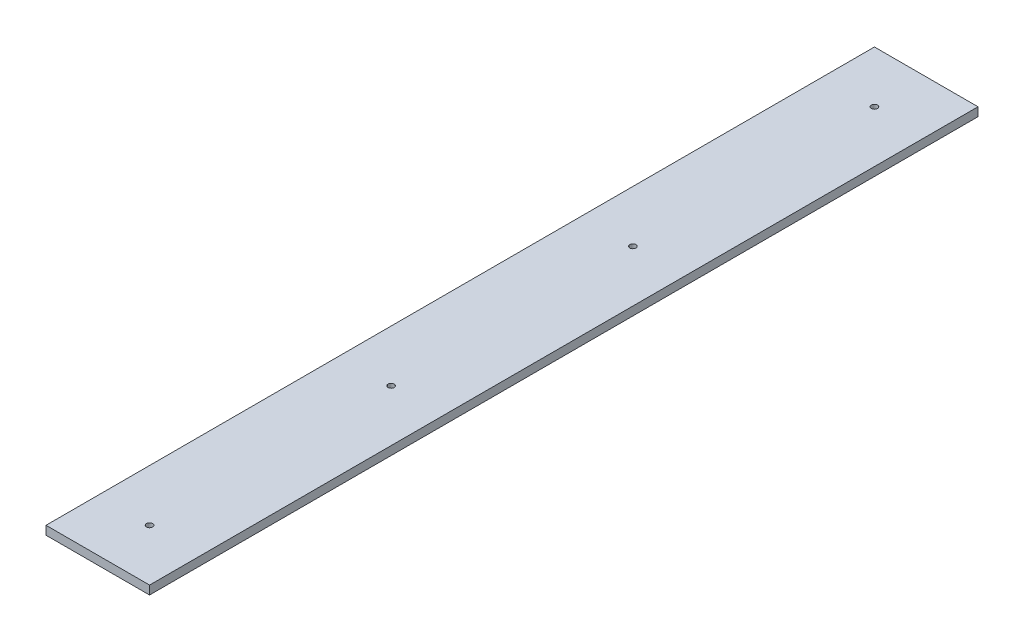
SolidWorks part; units mm, degrees
material "6061 Alloy"
ref_plane "Front Plane" through (0, 0, 0) normal (0, 0, 1) x (1, 0, 0)
ref_plane "Top Plane" through (0, 0, 0) normal (0, 1, 0) x (1, 0, 0)
ref_plane "Right Plane" through (0, 0, 0) normal (1, 0, 0) x (0, 0, -1)
sketch "Sketch1" plane through (0, 0, 0) normal (0, 1, 0) x (1, 0, 0)
  line L1 (0, 0) -> (76.2, 0)
  line L2 (0, 0) -> (0, 609.6)
  line L3 (0, 609.6) -> (76.2, 609.6)
  line L4 (76.2, 0) -> (76.2, 609.6)
  dimension "D1" = 609.6
  dimension "D2" = 76.2
extrude "Boss-Extrude1" add sketch "Sketch1" along normal blind 6.35
hole_wizard "#16 (0.177) Diameter Hole1" positions "Sketch2" profile "Sketch3" hole size "#16" standard "ANSI Inch" end condition through all
sketch "Sketch2" plane through (0, 6.35, 0) normal (0, 1, 0) x (1, 0, 0)
  line L0 (76.2, 609.6) -> (0, 609.6) construction
  line L1 (0, 0) -> (76.2, 0) construction
  line L2 (38.1, 0) -> (38.1, 609.6) construction
  point P0 (38.1, 38.1)
  point P2 (38.1, 215.9)
  point P4 (38.1, 393.7)
  point P6 (38.1, 571.5)
  dimension "D1" = 38.1
  dimension "D2" = 215.9
  dimension "D3" = 215.9
  dimension "D4" = 38.1
sketch "Sketch3" plane through (38.1, 6.35, -38.1) normal (1, 0, 0) x (0, 0, 1)
  line L0 (0, 0) -> (0, 6.35)
  line L1 (0, 6.35) -> (2.2479, 6.35)
  line L2 (2.2479, 6.35) -> (2.2479, 0)
  line L5 (2.2479, 0) -> (0, 0)
  line L11 (0, -6.35) -> (0, 107.95) construction
  dimension "Thru Hole Dia." = 4.4958
  dimension "Thru Hole Depth" = 6.35
